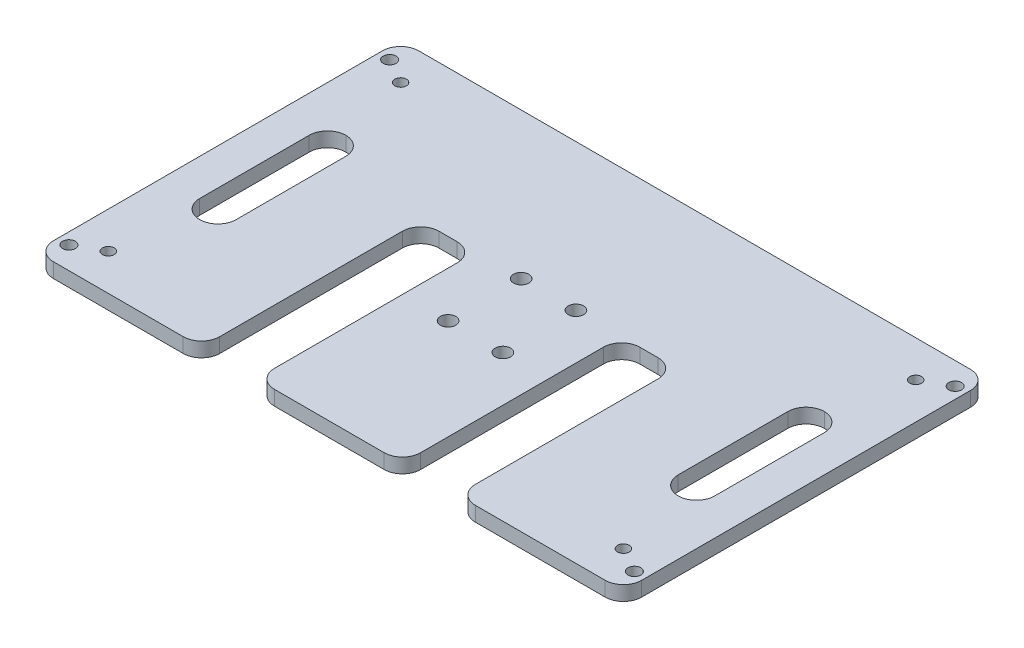
SolidWorks part; units mm, degrees
ref_plane "Front Plane" through (0, 0, 0) normal (0, 0, 1) x (1, 0, 0)
ref_plane "Top Plane" through (0, 0, 0) normal (0, 1, 0) x (1, 0, 0)
ref_plane "Right Plane" through (0, 0, 0) normal (1, 0, 0) x (0, 0, -1)
sketch "Sketch1" plane through (0, 0, 0) normal (0, 1, 0) x (1, 0, 0)
  line L1 (-80.5, -50) -> (80.5, -50)
  line L2 (-80.5, -50) -> (-80.5, 50)
  line L3 (-80.5, 50) -> (80.5, 50)
  line L4 (80.5, -50) -> (80.5, 50)
  line L5 (0, 50) -> (0, -50) construction
  line L6 (-80.5, 0) -> (80.5, 0) construction
  point P0 (0, 0)
  dimension "D1" = 100
  dimension "D2" = 161
extrude "Boss-Extrude1" add sketch "Sketch1" along normal blind 4
sketch "Sketch2" plane through (0, 4, 0) normal (0, 1, 0) x (1, 0, 0)
  line L0 (80.5, -50) -> (80.5, 50) construction
  line L1 (-80.5, -50) -> (80.5, -50) construction
  circle A0 centre (77.4, -43.9) radius 1.75
  dimension "D1" = 3.5
  dimension "D2" = 3.1
  dimension "D3" = 6.1
extrude "Cut-Extrude1" cut sketch "Sketch2" against normal through all
mirror "Mirror1" about plane through (0, 0, 0) normal (0, 0, 1) of "Cut-Extrude1"
mirror "Mirror2" about plane through (0, 0, 0) normal (1, 0, 0) of "Mirror1"
sketch "Sketch3" plane through (0, 4, 0) normal (0, 1, 0) x (1, 0, 0)
  line L0 (0, 50) -> (0, -50) construction
  line L1 (80.5, 50) -> (-80.5, 50) construction
  line L2 (-80.5, -50) -> (80.5, -50) construction
  line L4 (-35, 10) -> (-20, 10)
  line L5 (-35, 10) -> (-35, -50)
  line L6 (-35, -50) -> (-20, -50)
  line L7 (-20, 10) -> (-20, -50)
  line L8 (-27.5, -50) -> (-27.5, 10) construction
  line L9 (-35, -20) -> (-20, -20) construction
  point P6 (-27.5, -20)
  dimension "D1" = 15
  dimension "D2" = 20
  dimension "D3" = 60
extrude "Cut-Extrude2" cut sketch "Sketch3" against normal through all
mirror "Mirror3" about plane through (0, 0, 0) normal (1, 0, 0) of "Cut-Extrude2"
sketch "Sketch4" plane through (0, 4, 0) normal (0, 1, 0) x (1, 0, 0)
  line L0 (-80.5, 50) -> (-80.5, -50) construction
  line L1 (80.5, 50) -> (-80.5, 50) construction
  circle A0 centre (-70.5, 40) radius 1.6
  dimension "D1" = 3.2
  dimension "D2" = 10
  dimension "D3" = 10
extrude "Cut-Extrude3" cut sketch "Sketch4" against normal through all
mirror "Mirror4" about plane through (0, 0, 0) normal (0, 0, 1) of "Cut-Extrude3"
mirror "Mirror5" about plane through (0, 0, 0) normal (1, 0, 0) of "Mirror4"
sketch "Sketch5" plane through (0, 4, 0) normal (0, 1, 0) x (1, 0, 0)
  line L1 (-7.5, 10) -> (7.5, 10) construction
  line L2 (-7.5, 10) -> (-7.5, -10) construction
  line L3 (-7.5, -10) -> (7.5, -10) construction
  line L4 (7.5, 10) -> (7.5, -10) construction
  line L5 (0, -10) -> (0, 10) construction
  line L6 (-7.5, 0) -> (7.5, 0) construction
  circle A0 centre (-7.5, 10) radius 2.1
  circle A1 centre (7.5, 10) radius 2.1
  circle A2 centre (7.5, -10) radius 2.1
  circle A3 centre (-7.5, -10) radius 2.1
  point P0 (0, 0)
  dimension "D1" = 4.2
  dimension "D2" = 15
  dimension "D3" = 20
extrude "Cut-Extrude4" cut sketch "Sketch5" against normal through all
sketch "Sketch6" plane through (0, 4, 0) normal (0, 1, 0) x (1, 0, 0)
  line L0 (-80.5, 0) -> (80.5, 0) construction
  line L1 (-80.5, 50) -> (-80.5, -50) construction
  line L2 (80.5, -50) -> (80.5, 50) construction
  line L4 (-70.5, 20) -> (-60.5, 20)
  line L5 (-70.5, 20) -> (-70.5, -20)
  line L6 (-70.5, -20) -> (-60.5, -20)
  line L7 (-60.5, 20) -> (-60.5, -20)
  line L8 (-65.5, -20) -> (-65.5, 20) construction
  line L9 (-70.5, 0) -> (-60.5, 0) construction
  point P6 (-65.5, 0)
  dimension "D1" = 10
  dimension "D2" = 10
  dimension "D3" = 40
extrude "Cut-Extrude5" cut sketch "Sketch6" against normal through all
mirror "Mirror6" about plane through (0, 0, 0) normal (1, 0, 0) of "Cut-Extrude5"
fillet "Fillet1" radius 5 20 edges at (-20, 2, -10) (-35, 2, -10) (20, 2, -10) (35, 2, -10) (20, 2, 50) (35, 2, 50) (-20, 2, 50) (-35, 2, 50) (-80.5, 2, 50) (-80.5, 2, -50) (80.5, 2, -50) (80.5, 2, 50) (60.5, 2, -20) (70.5, 2, -20) (70.5, 2, 20) (60.5, 2, 20) (-70.5, 2, -20) (-60.5, 2, -20) (-60.5, 2, 20) (-70.5, 2, 20)
